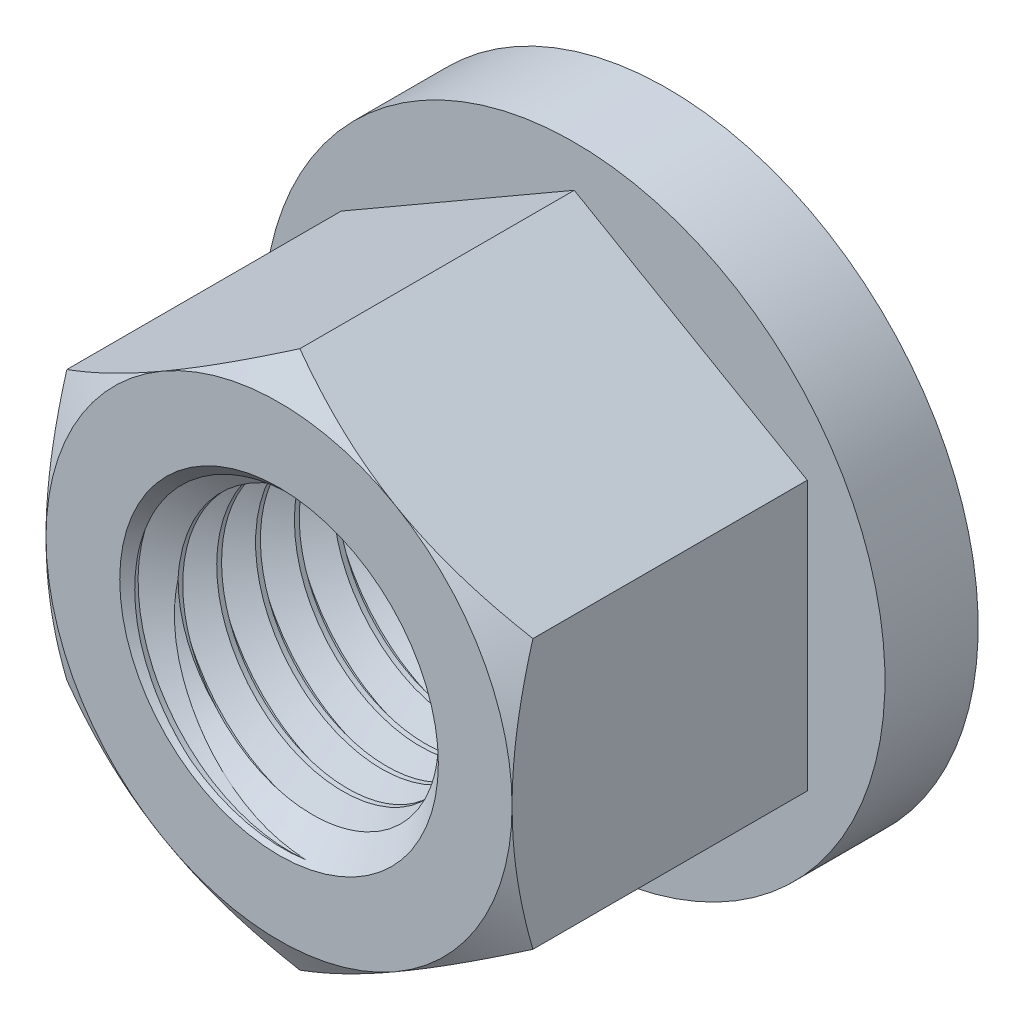
SolidWorks part; units mm, degrees
ref_plane "Front Plane" through (0, 0, 0) normal (0, 0, 1) x (1, 0, 0)
ref_plane "Top Plane" through (0, 0, 0) normal (0, 1, 0) x (1, 0, 0)
ref_plane "Right Plane" through (0, 0, 0) normal (1, 0, 0) x (0, 0, -1)
sketch "Sketch1" plane through (0, 0, 0) normal (0, 0, 1) x (1, 0, 0)
  line L1 (0, 17.3205) -> (-15, 8.6603)
  line L2 (-15, 8.6603) -> (-15, -8.6603)
  line L3 (-15, -8.6603) -> (0, -17.3205)
  line L4 (0, -17.3205) -> (15, -8.6603)
  line L5 (15, -8.6603) -> (15, 8.6603)
  line L6 (15, 8.6603) -> (0, 17.3205)
  circle A0 centre (0, 0) radius 15 construction
  dimension "Hex" = 30
extrude "Extrude1" add sketch "Sketch1" against normal blind 25
sketch "Sketch13" plane through (0, 0, -25) normal (0, 0, -1) x (-1, 0, 0)
  circle A0 centre (0, 0) radius 20
  dimension "Flange od" = 40
extrude "Extrude3" add sketch "Sketch13" against normal blind 6
sketch "Sketch2" plane through (0, 0, 0) normal (0, 0, 1) x (1, 0, 0)
  circle A0 centre (0, 0) radius 15 construction
  circle A1 centre (0, 0) radius 15
extrude "Cut-Extrude1" cut sketch "Sketch2" against normal through all draft 60 flip side to cut
sketch "Sketch4" plane through (0, 0, 0) normal (0, 0, 1) x (1, 0, 0)
  circle A0 centre (0, 0) radius 10
  dimension "Thread Dia" = 20
extrude "Cut-Extrude3" cut sketch "Sketch4" against normal through all
sketch "Sketch7" plane through (0, 0, 0) normal (0, 0, 1) x (1, 0, 0)
  circle A4 centre (0, 0) radius 10.254
  circle A5 centre (0, 0) radius 10.254
  dimension "D1" = 0.254
sketch "Sketch8" plane through (0, 0, -25) normal (0, 0, -1) x (-1, 0, 0)
  circle A1 centre (0, 0) radius 10.254
  circle A2 centre (0, 0) radius 10.254 construction
sketch "Sketch5" plane through (0, 0, 0) normal (0, 0, 1) x (1, 0, 0)
  circle A0 centre (0, 0) radius 10 construction
  circle A1 centre (0, 0) radius 10
curve "Helix/Spiral1" pitch 2.5 height 27.5 turns 11 parameters "pitch"=2.5
sketch "Sketch9" plane through (0, 0, 0) normal (1, 0, 0) x (0, 0, -1)
  line L0 (-1.25, 10) -> (-0.9375, 10)
  line L1 (-0.9375, 10) -> (0, 8.3762)
  line L2 (-1.25, 10) -> (-2.1875, 8.3762)
  line L3 (-2.1875, 8.3762) -> (0, 8.3762)
  line L4 (-1.0938, 10) -> (-1.0938, 8.3762) construction
  line L5 (-1.7188, 9.1881) -> (-0.4688, 9.1881) construction
  line L7 (0, 8.3762) -> (0, 10) construction
  line L8 (0, 10) -> (0, -10) construction
  dimension "D1" = 0.3125
  dimension "D2" = 1.25
  dimension "D3" = 60
sketch "Sketch12" plane through (0, 0, 0) normal (0, 0, 1) x (1, 0, 0)
  circle A0 centre (0, 0) radius 8.3762
  circle A1 centre (0, 0) radius 10 construction
  circle A2 centre (0, 0) radius 10
extrude "Extrude2" add sketch "Sketch12" against normal up to surface (25 mm away) up to face at (10, 0, -25)
sweep "Cut-Sweep1" cut profiles "Sketch9" path "Helix/Spiral1"
extrude "Cut-Extrude6" cut sketch "Sketch7" against normal through all draft 45
extrude "Cut-Extrude7" cut sketch "Sketch8" against normal through all draft 45
equation "\"D2@Sketch9\" = \"pitch@Helix/Spiral1\"*.5"
equation "\"D3@Helix/Spiral1\" = \"pitch@Helix/Spiral1\"+\"Height@Extrude1\""
equation "\"D1@Sketch9\" = \"pitch@Helix/Spiral1\"*.125"
